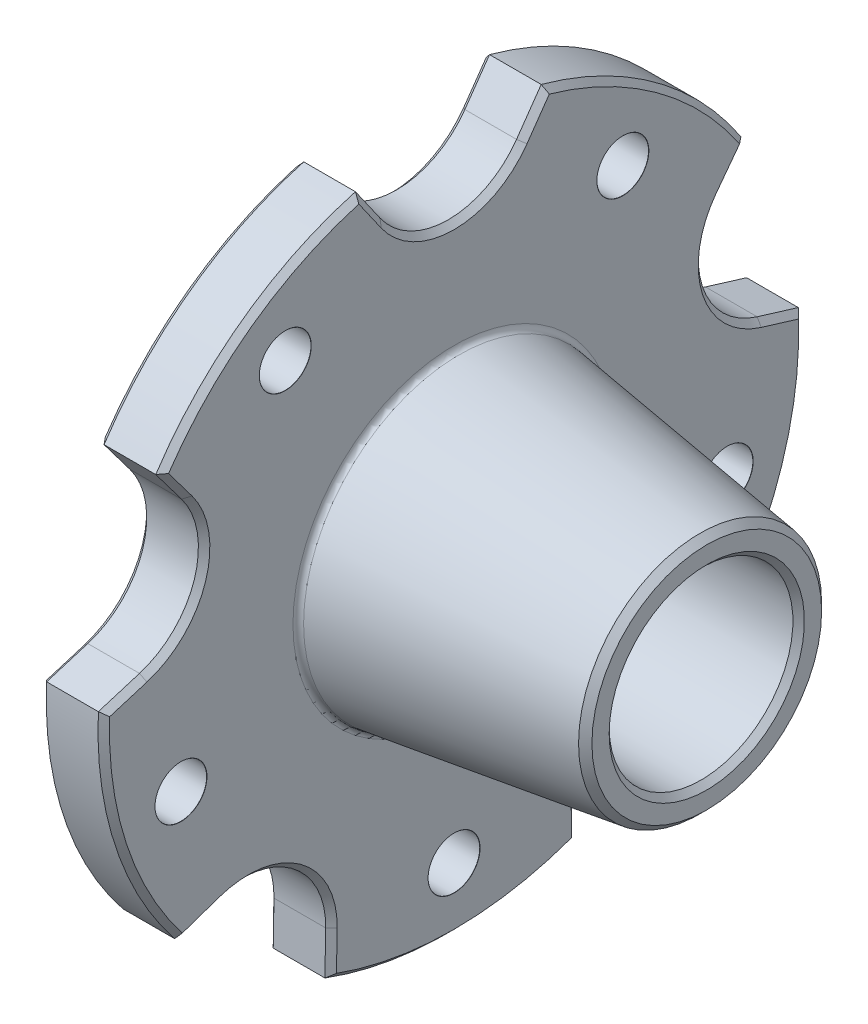
SolidWorks part; units mm, degrees
material "Plain Carbon Steel"
ref_plane "Front Plane" through (0, 0, 0) normal (0, 0, 1) x (1, 0, 0)
ref_plane "Top Plane" through (0, 0, 0) normal (0, 1, 0) x (1, 0, 0)
ref_plane "Right Plane" through (0, 0, 0) normal (1, 0, 0) x (0, 0, -1)
sketch "Sketch1" plane through (0, 0, 0) normal (0, 0, 1) x (1, 0, 0)
  line L0 (0, 12) -> (0, 25)
  line L1 (0, 25) -> (15, 25)
  line L2 (15, 25) -> (15, 61)
  line L3 (15, 61) -> (26, 61)
  line L4 (26, 61) -> (26, 27.1838)
  line L5 (26, 27.1838) -> (70, 21)
  line L6 (70, 21) -> (70, 16)
  line L7 (70, 16) -> (38, 16)
  line L8 (38, 16) -> (38, 8)
  line L9 (38, 8) -> (12, 8)
  line L10 (12, 8) -> (12, 12)
  line L11 (12, 12) -> (0, 12)
  line L12 (0, 0) -> (38, 0) construction
  dimension "D1" = 8
  dimension "D2" = 12
  dimension "D3" = 12
  dimension "D4" = 15
  dimension "D5" = 26
  dimension "D6" = 38
  dimension "D7" = 70
  dimension "D8" = 16
  dimension "D9" = 21
  dimension "D10" = 8
  dimension "D11" = 25
  dimension "D12" = 61
revolve "Revolve1" add sketch "Sketch1" angle 360 about L12
sketch "Sketch3" plane through (15, 0, 0) normal (-1, 0, 0) x (0, 0, 1)
  line L0 (0, 0) -> (0, 61) construction
  line L1 (-11.8777, 52.6831) -> (-16.1727, 58.817)
  line L2 (11.8777, 52.6831) -> (16.1727, 58.817)
  circle A0 centre (0, 0) radius 61 construction
  arc A1 (16.1727, 58.817) -> (-16.1727, 58.817) centre (0, 0) ccw
  arc A2 (-11.8777, 52.6831) -> (11.8777, 52.6831) centre (0, 61) ccw
  dimension "D1" = 29
  dimension "D2" = 35
  dimension "D3" = 70
extrude "Cut-Extrude2" cut sketch "Sketch3" against normal up to next
fillet "Fillet1" radius 1 4 edges at (38, 0, 16) (26, 0, 27.1838) (15, 0, 25) (12, 0, 12)
sketch "Sketch4" plane through (15, 0, 0) normal (-1, 0, 0) x (0, 0, 1)
  line L0 (0, 0) -> (0, 50) construction
  line L1 (0, 0) -> (-29.3893, 40.4508) construction
  circle A0 centre (0, 0) radius 50 construction
  dimension "D1" = 100
  dimension "D2" = 36
hole_wizard "M3 Clearance Hole2" positions "3DSketch2" profile "Sketch6" hole size "M3" standard "ISO" end condition up to next
sketch3d "3DSketch2"
  point P0 (15, 40.4508, -29.3893)
sketch "Sketch6" plane through (15, 40.4508, -29.3893) normal (0, 1, 0) x (0, 0, 1)
  line L0 (0, 0) -> (0, 11)
  line L1 (0, 11) -> (4.525, 11)
  line L2 (4.5, 10.975) -> (4.5, 0.025)
  line L3 (4.5, 0.025) -> (4.525, 0)
  line L5 (4.525, 0) -> (0, 0)
  line L6 (-4.5, 0.025) -> (-4.525, 0) construction
  line L7 (4.525, 11) -> (4.5, 10.975)
  line L8 (-4.525, 11) -> (-4.5, 10.975) construction
  line L11 (0, -6.35) -> (0, 107.95) construction
  dimension "Thru Hole Dia." = 9
  dimension "Thru Hole Depth" = 11
  dimension "Near C'Sink Dia." = 9.05
  dimension "Near C'Sink Angle" = 90
  dimension "Far C'Sink Dia." = 9.05
  dimension "Far C'Sink Angle" = 90
pattern_circular "CirPattern6" count 5 over 360 about axis through (0, 0, 0) along (-1, 0, 0) of "Cut-Extrude2", "M3 Clearance Hole2" reverse direction yes
chamfer "Chamfer2" distance 1 angle 45 46 edges at (12, 0, 8) (38, 0, 8) (70, 0, 16) (70, 0, 21) (26, 55.7501, 14.0252) (26, 55.7501, -14.0252) (26, 46.5, 0) (15, 55.7501, -14.0252) (15, 55.7501, 14.0252) (15, 46.5, 0) (26, 49.35, -35.8549) (26, 49.35, 35.8549) (15, 49.35, 35.8549) (15, 49.35, -35.8549) (0, 0, 12) (0, 0, 25) (15, 30.5665, 48.6875) (15, 3.889, 57.3555) (15, 14.3693, 44.2241) (26, 3.889, 57.3555) (26, 30.5665, 48.6875) (26, 14.3693, 44.2241) (26, 30.5665, -48.6875) (26, 3.889, -57.3555) (26, 14.3693, -44.2241) (15, 3.889, -57.3555) (15, 30.5665, -48.6875) (15, 14.3693, -44.2241) (26, -18.85, -58.0144) (15, -18.85, -58.0144) (26, -36.859, -44.1157) (26, -53.3466, -21.4225) (26, -37.6193, -27.332) (15, -53.3466, -21.4225) (15, -36.859, -44.1157) (15, -37.6193, -27.332) (26, -61, 0) (15, -61, 0) (15, -36.859, 44.1157) (15, -53.3466, 21.4225) (15, -37.6193, 27.332) (26, -53.3466, 21.4225) (26, -36.859, 44.1157) (26, -37.6193, 27.332) (26, -18.85, 58.0144) (15, -18.85, 58.0144) first distance on face at (12, 0, -11) first distance on face at (38, 0, 8) first distance on face at (39, 0, 16) first distance on face at (70, 0, 21) first distance on face at (26, 36.1473, 30.7876) first distance on face at (20.5, 55.7501, -14.0252) first distance on face at (20.5, 55.7501, 14.0252) first distance on face at (20.5, 49.5916, 0) first distance on face at (20.5, 47.7684, 34.7058) first distance on face at (20.5, 47.7684, -34.7058) first distance on face at (11, 0, -12) first distance on face at (14, 0, -25) first distance on face at (20.5, 30.5665, 48.6875) first distance on face at (20.5, 3.889, 57.3555) first distance on face at (20.5, 15.3246, 47.1644) first distance on face at (20.5, 3.889, -57.3555) first distance on face at (20.5, 30.5665, -48.6875) first distance on face at (20.5, 15.3246, -47.1644) first distance on face at (20.5, -18.2459, -56.1552) first distance on face at (20.5, -53.3466, -21.4225) first distance on face at (20.5, -36.859, -44.1157) first distance on face at (20.5, -40.1204, -29.1492) first distance on face at (20.5, -59.045, 0) first distance on face at (20.5, -36.859, 44.1157) first distance on face at (20.5, -53.3466, 21.4225) first distance on face at (20.5, -40.1204, 29.1492) first distance on face at (20.5, -18.2459, 56.1552)
